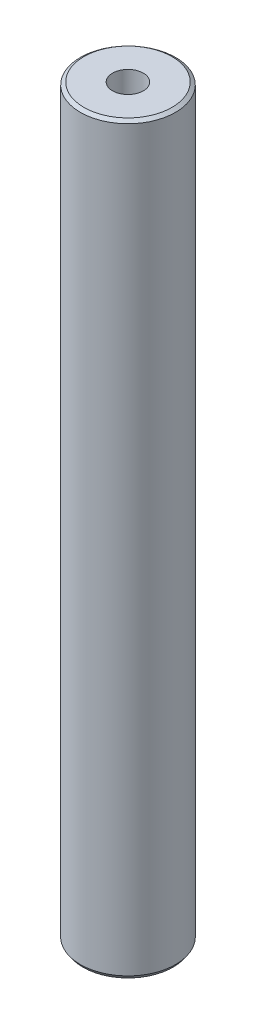
SolidWorks part; units mm, degrees
ref_plane "Front Plane" through (0, 0, 0) normal (0, 0, 1) x (1, 0, 0)
ref_plane "Top Plane" through (0, 0, 0) normal (0, 1, 0) x (1, 0, 0)
ref_plane "Right Plane" through (0, 0, 0) normal (1, 0, 0) x (0, 0, -1)
sketch "Sketch1" plane through (0, 0, 0) normal (0, 1, 0) x (1, 0, 0)
  circle A0 centre (0, 0) radius 35
  dimension "SHAFT_OD" = 70
extrude "Boss-Extrude1" add sketch "Sketch1" along normal blind 546.9826
sketch "Sketch2" plane through (0, 0, 0) normal (0, 1, 0) x (1, 0, 0)
  circle A0 centre (0, 0) radius 11.3221
  dimension "BORE_D" = 22.6442
extrude "Cut-Extrude1" cut sketch "Sketch2" along normal through all
chamfer "Chamfer1" distance 1.8377 angle 55.055 2 edges at (0, 546.9826, 35) (0, 0, 35) first distance on face at (0, 546.9826, 35) first distance on face at (0, 0, 11.3221)
